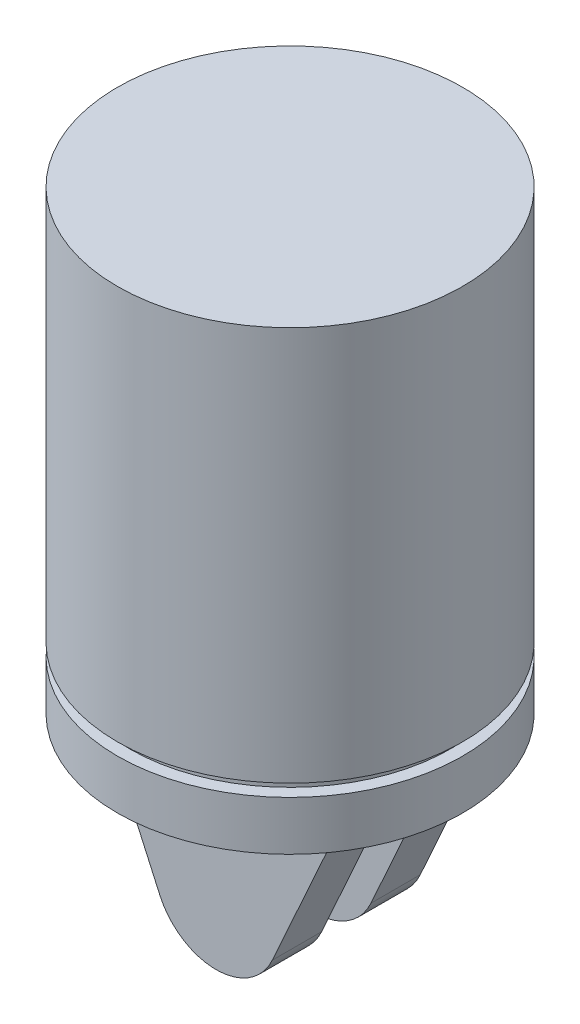
SolidWorks part; units mm, degrees
ref_plane "Front Plane" through (0, 0, 0) normal (0, 0, 1) x (1, 0, 0)
ref_plane "Top Plane" through (0, 0, 0) normal (0, 1, 0) x (1, 0, 0)
ref_plane "Right Plane" through (0, 0, 0) normal (1, 0, 0) x (0, 0, -1)
sketch "Sketch1" plane through (0, 0, 0) normal (0, 0, 1) x (1, 0, 0)
  line L0 (-11.393, -5.143) -> (-25, 25)
  line L1 (-25, 25) -> (25, 25)
  line L2 (25, 25) -> (11.393, -5.143)
  arc A0 (-11.393, -5.143) -> (11.393, -5.143) centre (0, 0) ccw
  arc A1 (11.393, -5.143) -> (-11.393, -5.143) centre (0, 0) ccw construction
  point P5 (0, 25)
  point P8 (23.6599, 35.765)
  point P9 (-25, 42.4901)
  dimension "D1" = 25
  dimension "D2" = 50
  dimension "D3" = 25
extrude "Boss-Extrude1" add sketch "Sketch1" along normal blind 10 from offset 5
pattern_linear "LPattern1" count 2 spacing 20 along (0, 0, -1) of bodies 101
sketch "Sketch2" plane through (0, 25, 0) normal (0, 1, 0) x (1, 0, 0)
  circle A0 centre (0, 0) radius 35
  circle A1 centre (0, 0) radius 32.5
  line M1 (25, -5) -> (-25, -5)
  line M2 (-25, -5) -> (-25, -15)
  line M3 (-25, -15) -> (25, -15)
  line M4 (25, -15) -> (25, -5)
  dimension "D1" = 70
  dimension "D2" = 2.5
extrude "Boss-Extrude2" add sketch "Sketch2" along normal blind 10 contours M4 M1 M2 M3 | A1 M1 M4 M3 M2 | A0 A1 region at (-34.0101, 25, 0) region at (0, 25, -1.7741) region at (0, 25, 10)
extrude "Boss-Extrude3" add sketch "Sketch2<3>" along normal blind 2.5 from surface contours A1 starting at face at (0, 35, 35)
sketch "Sketch2<3>" plane through (0, 25, 0) normal (0, 1, 0) x (1, 0, 0) same geometry as "Sketch2"
extrude "Boss-Extrude4" add sketch "Sketch2<4>" along normal blind 80 from surface contours A0 starting at face at (0, 37.5, 32.5)
sketch "Sketch2<4>" plane through (0, 25, 0) normal (0, 1, 0) x (1, 0, 0) same geometry as "Sketch2"
